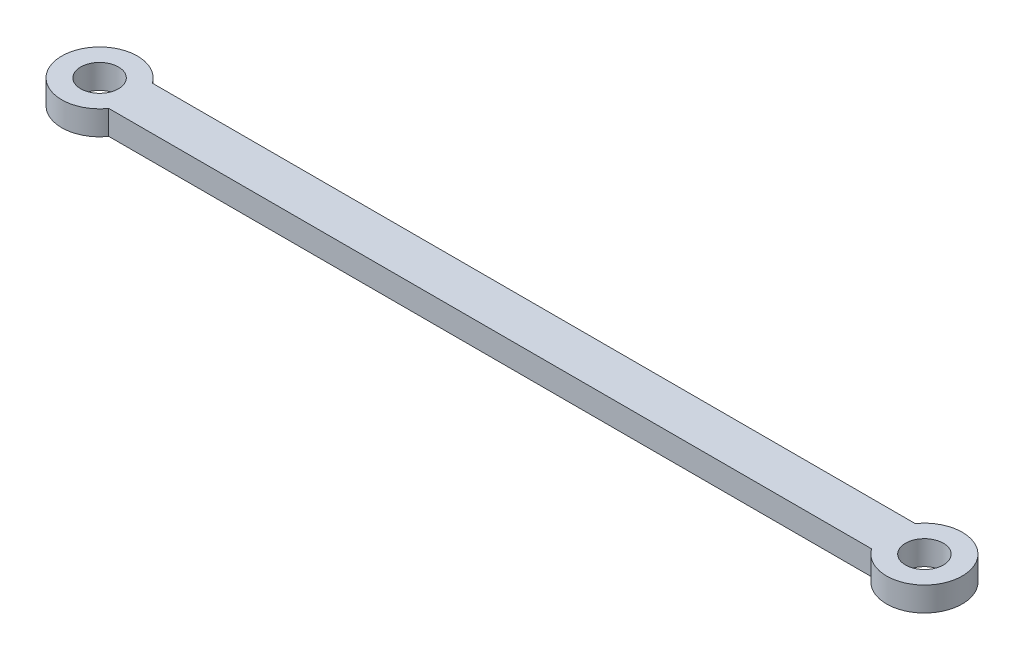
SolidWorks part; units mm, degrees
material "Acrylic (Medium-high impact)"
ref_plane "Front Plane" through (0, 0, 0) normal (0, 0, 1) x (1, 0, 0)
ref_plane "Top Plane" through (0, 0, 0) normal (0, 1, 0) x (1, 0, 0)
ref_plane "Right Plane" through (0, 0, 0) normal (1, 0, 0) x (0, 0, -1)
sketch "Sketch1" plane through (0, 0, 0) normal (0, 1, 0) x (1, 0, 0)
  line L0 (0, 0) -> (78.3381, 0) construction
  line L1 (0, 0) -> (0, 51263.8953) construction
  line L2 (-78.6164, -4.5) -> (78.6164, -4.5)
  line L3 (-78.6164, 4.5) -> (78.6164, 4.5)
  circle A0 centre (85, 0) radius 3.9
  arc A1 (78.6164, -4.5) -> (78.6164, 4.5) centre (85, 0) ccw
  arc A2 (-78.6164, -4.5) -> (-78.6164, 4.5) centre (-85, 0) cw
  circle A3 centre (-85, 0) radius 3.9
  point P10 (0, -4.5)
  point P17 (0, 4.5)
  dimension "D2" = 7.8
  dimension "D1" = 7.8102
  dimension "D3" = 4.5
  dimension "D4" = 85
extrude "Boss-Extrude1" add sketch "Sketch1" along normal blind 5
